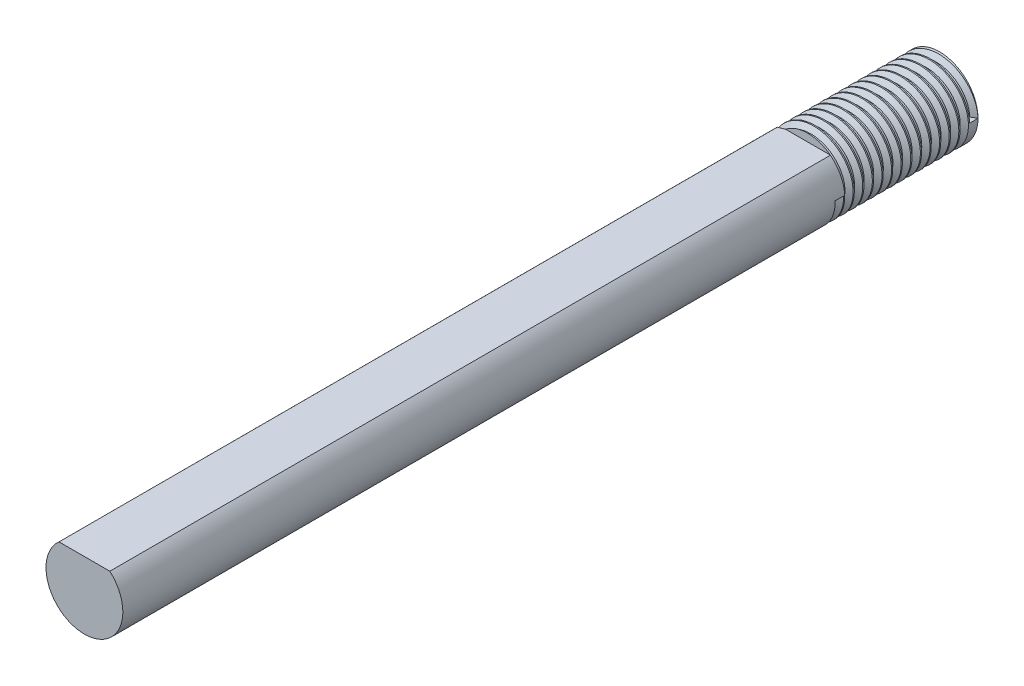
SolidWorks part; units mm, degrees
ref_plane "Front Plane" through (0, 0, 0) normal (0, 0, 1) x (1, 0, 0)
ref_plane "Top Plane" through (0, 0, 0) normal (0, 1, 0) x (1, 0, 0)
ref_plane "Right Plane" through (0, 0, 0) normal (1, 0, 0) x (0, 0, -1)
sketch "Sketch1" plane through (0, 0, 0) normal (0, 0, 1) x (1, 0, 0)
  circle A0 centre (0, 0) radius 4
  dimension "D1" = 8
extrude "Boss-Extrude1" add sketch "Sketch1" along normal blind 89
sketch "Sketch3" plane through (0, 0, 0) normal (0, 1, 0) x (1, 0, 0)
  line L0 (0, -89) -> (0, 0) construction
  line L1 (-4, -89) -> (4, -89) construction
  line L3 (3, -89) -> (-3, -89)
  line L4 (3, -89) -> (3, -14)
  line L5 (3, -14) -> (-3, -14)
  line L6 (-3, -89) -> (-3, -14)
  dimension "D1" = 75
  dimension "D2" = 6
extrude "Cut-Extrude1" cut sketch "Sketch3" along normal through all from offset 3
thread "Thread1" pitch 1 method cut profile "Thread Profile1" start angle 0, offset 0, length 14, pitch 1, diameter 8
ref_plane "Plane1" through (4, 0, 0) normal (0, -1, 0) x (1, 0, 0)
sketch "Thread Profile1" plane through (4, 0, 0) normal (0, -1, 0) x (1, 0, 0)
  line L0 (0, 0) -> (0, 1) construction
  line L11 (0, 0) -> (0, 0.875)
  line L12 (0, 0.875) -> (-0.5413, 0.5625)
  line L13 (-0.5413, 0.5625) -> (-0.5413, 0.3125)
  line L15 (-0.5413, 0.3125) -> (0, 0)
  line L17 (-0.5413, 0.4375) -> (0, 0.4375) construction
  point P2 (0, 0)
  dimension "Pitch" = 1
  dimension "Profile_Angle" = 60
  dimension "Profile_Land" = 0.25
  dimension "Profile_Height" = 0.5413
